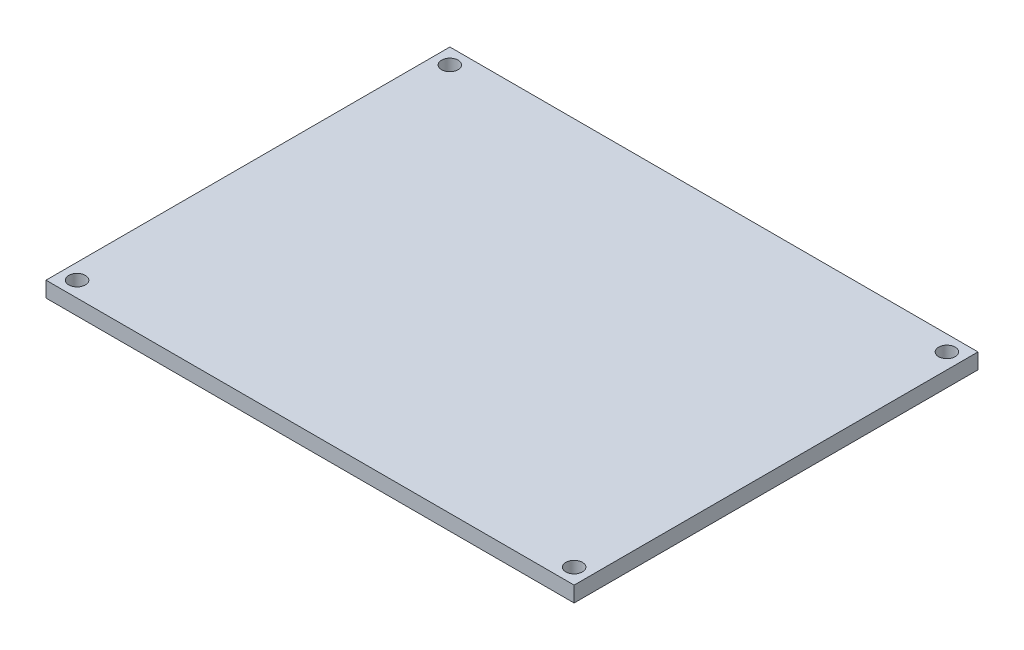
SolidWorks part; units mm, degrees
material "6061 Alloy"
ref_plane "Front Plane" through (0, 0, 0) normal (0, 0, 1) x (1, 0, 0)
ref_plane "Top Plane" through (0, 0, 0) normal (0, 1, 0) x (1, 0, 0)
ref_plane "Right Plane" through (0, 0, 0) normal (1, 0, 0) x (0, 0, -1)
sketch "Sketch1" plane through (0, 0, 0) normal (0, 1, 0) x (1, 0, 0)
  line L0 (-53.975, 41.275) -> (53.975, 41.275)
  line L1 (-50.8, -38.1) -> (50.8, -38.1) construction
  line L2 (-50.8, -38.1) -> (-50.8, 38.1) construction
  line L3 (-50.8, 38.1) -> (50.8, 38.1) construction
  line L4 (50.8, -38.1) -> (50.8, 38.1) construction
  line L5 (-50.8, -38.1) -> (50.8, 38.1) construction
  line L6 (-50.8, 38.1) -> (50.8, -38.1) construction
  line L7 (53.975, -41.275) -> (53.975, 41.275)
  line L8 (-53.975, -41.275) -> (53.975, -41.275)
  line L9 (-53.975, -41.275) -> (-53.975, 41.275)
  point P0 (0, 0)
  dimension "D1" = 101.6
  dimension "D2" = 76.2
  dimension "D3" = 3.175
extrude "Boss-Extrude1" add sketch "Sketch1" along normal blind 3.175
hole_wizard "M3 Clearance Hole1" positions "3DSketch1" profile "Sketch2" hole size "M3" standard "ANSI Metric" end condition through all
sketch3d "3DSketch1"
  point P0 (-50.8, 0, 38.1)
  point P3 (50.8, 0, 38.1)
  point P6 (-50.8, 0, -38.1)
  point P9 (50.8, 0, -38.1)
sketch "Sketch2" plane through (-50.8, 0, 38.1) normal (1, 0, 0) x (0, 0, -1)
  line L0 (0, 0) -> (0, 3.175)
  line L1 (0, 3.175) -> (1.7, 3.175)
  line L2 (1.7, 3.175) -> (1.7, 0)
  line L5 (1.7, 0) -> (0, 0)
  line L11 (0, -6.35) -> (0, 107.95) construction
  dimension "Thru Hole Dia." = 3.4
  dimension "Thru Hole Depth" = 3.175
